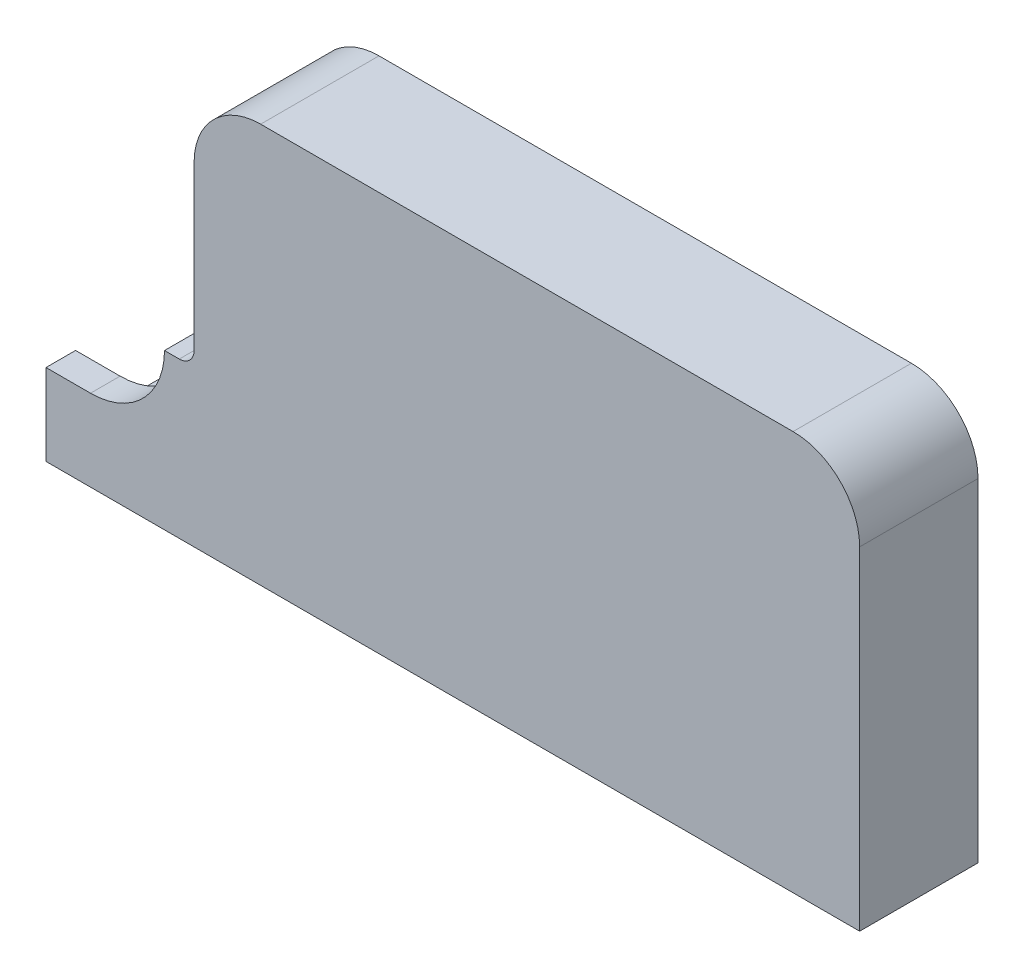
SolidWorks part; units mm, degrees
ref_plane "Front Plane" through (0, 0, 0) normal (0, 0, 1) x (1, 0, 0)
ref_plane "Top Plane" through (0, 0, 0) normal (0, 1, 0) x (1, 0, 0)
ref_plane "Right Plane" through (0, 0, 0) normal (1, 0, 0) x (0, 0, -1)
sketch "Sketch1" plane through (0, 0, 0) normal (0, 0, 1) x (1, 0, 0)
  line L30 (11.5095, 13.5276) -> (11.5095, 22.5276)
  line L31 (15.0095, 26.0276) -> (51, 26.0276)
  line L32 (54.5, 22.5276) -> (54.5, 1.0276)
  line L33 (54.5, 1.0276) -> (1.5, 1.0276)
  line L35 (0.5, 0.0276) -> (0.5, 5.5276)
  line L36 (55.5, 0.0276) -> (0.5, 0.0276)
  line L37 (55.5, 22.5276) -> (55.5, 0.0276)
  line L38 (15.0095, 27.0276) -> (51, 27.0276)
  line L39 (10.5095, 11.5276) -> (10.5095, 22.5276)
  line L40 (0.5, 0.0276) -> (0.5, 1.0276)
  line L41 (55.5, 0.0276) -> (0.5, 0.0276)
  line L42 (55.5, 22.5276) -> (55.5, 0.0276)
  line L43 (15.0095, 27.0276) -> (51, 27.0276)
  line L44 (10.5095, 13.5276) -> (10.5095, 22.5276)
  line L46 (10.5095, 13.5276) -> (11.5095, 13.5276)
  line L47 (8.5095, 11.5276) -> (10.0095, 11.5276) construction
  line L48 (10.5095, 11.5276) -> (10.5095, 22.5276) construction
  line L49 (11.5095, 11.5276) -> (11.5095, 22.5276) construction
  line L50 (1.5, 1.0276) -> (0.5, 1.0276)
  line L52 (0.5, 0.0276) -> (0.5, 5.5276) construction
  line L55 (1.5, 1.0276) -> (1.5, 5.5276) construction
  arc A13 (15.0095, 26.0276) -> (11.5095, 22.5276) centre (15.0095, 22.5276) ccw
  arc A14 (54.5, 22.5276) -> (51, 26.0276) centre (51, 22.5276) ccw
  arc A15 (55.5, 22.5276) -> (51, 27.0276) centre (51, 22.5276) ccw
  arc A16 (15.0095, 27.0276) -> (10.5095, 22.5276) centre (15.0095, 22.5276) ccw
  arc A17 (55.5, 22.5276) -> (51, 27.0276) centre (51, 22.5276) ccw
  arc A18 (15.0095, 27.0276) -> (10.5095, 22.5276) centre (15.0095, 22.5276) ccw
  dimension "D3" = 2
  dimension "D1" = 0.5
  dimension "D2" = 1
extrude "Boss-Extrude1" add sketch "Sketch1" along normal up to surface (8 mm away) from offset 5
sketch "Sketch2" plane through (0, 0, 13) normal (0, 0, 1) x (1, 0, 0)
  line L0 (0.5, 5.5276) -> (8.5095, 5.5276)
  line L1 (8.5095, 5.5276) -> (8.5095, 10.5276)
  line L2 (8.5095, 5.5276) -> (8.5095, 11.5276) construction
  line L3 (8.5095, 10.5276) -> (10.5095, 10.5276)
  line L4 (10.5095, 10.5276) -> (10.5095, 13.5276)
  line L5 (8.5095, 11.5276) -> (10.0095, 11.5276) construction
  line L6 (10.5095, 22.5276) -> (10.5095, 13.5276) construction
  line L7 (0.5, 1.0276) -> (0.5, 5.5276)
  line L8 (0, 5.5276) -> (3.5095, 5.5276) construction
  line L19 (11.5095, 13.5276) -> (11.5095, 22.5276)
  line L20 (15.0095, 26.0276) -> (51, 26.0276)
  line L21 (54.5, 22.5276) -> (54.5, 1.0276)
  line L22 (54.5, 1.0276) -> (0.5, 1.0276)
  line L25 (0.5, 1.0276) -> (0.5, 0.0276)
  line L26 (0.5, 0.0276) -> (55.5, 0.0276)
  line L27 (55.5, 0.0276) -> (55.5, 22.5276)
  line L28 (51, 27.0276) -> (15.0095, 27.0276)
  line L29 (10.5095, 22.5276) -> (10.5095, 13.5276)
  line L30 (10.5095, 13.5276) -> (11.5095, 13.5276)
  line L37 (0.5, 1.0276) -> (0.5, 0.0276)
  line L38 (0.5, 0.0276) -> (55.5, 0.0276)
  line L39 (55.5, 0.0276) -> (55.5, 22.5276)
  line L40 (51, 27.0276) -> (15.0095, 27.0276)
  line L41 (10.5095, 22.5276) -> (10.5095, 13.5276)
  arc A4 (15.0095, 26.0276) -> (11.5095, 22.5276) centre (15.0095, 22.5276) ccw
  arc A5 (54.5, 22.5276) -> (51, 26.0276) centre (51, 22.5276) ccw
  arc A6 (55.5, 22.5276) -> (51, 27.0276) centre (51, 22.5276) ccw
  arc A7 (15.0095, 27.0276) -> (10.5095, 22.5276) centre (15.0095, 22.5276) ccw
  arc A10 (55.5, 22.5276) -> (51, 27.0276) centre (51, 22.5276) ccw
  arc A11 (15.0095, 27.0276) -> (10.5095, 22.5276) centre (15.0095, 22.5276) ccw
  dimension "D1" = 1
  dimension "D2" = 0
extrude "Boss-Extrude2" add sketch "Sketch2" against normal blind 2
sketch "Sketch3" plane through (0, 0, 13) normal (0, 0, 1) x (1, 0, 0)
  circle A0 centre (29.6764, 8.283) radius 2 construction
  circle A1 centre (29.6764, 8.283) radius 2
extrude "Cut-Extrude1" [suppressed] cut sketch "Sketch3" against normal up to next
fillet "Fillet1" radius 5 1 edges at (8.5095, 5.5276, 12)
fillet "Fillet2" radius 1 1 edges at (10.5095, 10.5276, 12)
fillet "Fillet3" radius 1 6 edges at (11.5095, 18.0276, 11) (12.5346, 25.0024, 11) (54.5, 11.7776, 11) (53.4749, 25.0024, 11) (27.5, 1.0276, 11) (33.0047, 26.0276, 11)
sketch "Sketch4" plane through (0, 0, 13) normal (0, 0, 1) x (1, 0, 0)
  line L7 (10.5095, 22.5276) -> (10.5095, 11.5276)
  line L8 (9.5095, 10.5276) -> (8.5095, 10.5276)
  line L9 (3.5095, 5.5276) -> (0.5, 5.5276)
  line L10 (0.5, 5.5276) -> (0.5, 0.0276)
  line L11 (0.5, 0.0276) -> (55.5, 0.0276)
  line L12 (55.5, 0.0276) -> (55.5, 22.5276)
  line L13 (51, 27.0276) -> (15.0095, 27.0276)
  line L14 (10.5095, 22.5276) -> (10.5095, 11.5276)
  line L15 (9.5095, 10.5276) -> (8.5095, 10.5276)
  line L16 (3.5095, 5.5276) -> (0.5, 5.5276)
  line L17 (0.5, 5.5276) -> (0.5, 0.0276)
  line L18 (0.5, 0.0276) -> (55.5, 0.0276)
  line L19 (55.5, 0.0276) -> (55.5, 22.5276)
  line L20 (51, 27.0276) -> (15.0095, 27.0276)
  arc A4 (9.5095, 10.5276) -> (10.5095, 11.5276) centre (9.5095, 11.5276) ccw
  arc A5 (3.5095, 5.5276) -> (8.5095, 10.5276) centre (3.5095, 10.5276) ccw
  arc A6 (55.5, 22.5276) -> (51, 27.0276) centre (51, 22.5276) ccw
  arc A7 (15.0095, 27.0276) -> (10.5095, 22.5276) centre (15.0095, 22.5276) ccw
  arc A8 (9.5095, 10.5276) -> (10.5095, 11.5276) centre (9.5095, 11.5276) ccw
  arc A9 (3.5095, 5.5276) -> (8.5095, 10.5276) centre (3.5095, 10.5276) ccw
  arc A10 (55.5, 22.5276) -> (51, 27.0276) centre (51, 22.5276) ccw
  arc A11 (15.0095, 27.0276) -> (10.5095, 22.5276) centre (15.0095, 22.5276) ccw
  dimension "D1" = 0
sketch "Sketch6" plane through (0, 0, 13) normal (0, 0, 1) x (1, 0, 0)
  line L0 (30.8689, 19.9892) -> (35.2853, 19.9892) construction
  line L1 (30.8689, 21.681) -> (35.2853, 21.681) construction
  line L2 (30.8689, 18.2974) -> (35.2853, 18.2974) construction
  line L3 (30.8689, 22.681) -> (35.2853, 22.681)
  line L4 (30.8689, 17.2974) -> (35.2853, 17.2974)
  line L7 (10.5095, 22.5276) -> (10.5095, 11.5276)
  line L8 (9.5095, 10.5276) -> (8.5095, 10.5276)
  line L9 (3.5095, 5.5276) -> (0.5, 5.5276)
  line L10 (0.5, 5.5276) -> (0.5, 0.0276)
  line L11 (0.5, 0.0276) -> (55.5, 0.0276)
  line L12 (55.5, 0.0276) -> (55.5, 22.5276)
  line L13 (51, 27.0276) -> (15.0095, 27.0276)
  line L14 (10.5095, 22.5276) -> (10.5095, 11.5276)
  line L15 (9.5095, 10.5276) -> (8.5095, 10.5276)
  line L16 (3.5095, 5.5276) -> (0.5, 5.5276)
  line L17 (0.5, 5.5276) -> (0.5, 0.0276)
  line L18 (0.5, 0.0276) -> (55.5, 0.0276)
  line L19 (55.5, 0.0276) -> (55.5, 22.5276)
  line L20 (51, 27.0276) -> (15.0095, 27.0276)
  arc A0 (30.8689, 21.681) -> (30.8689, 18.2974) centre (30.8689, 19.9892) ccw construction
  arc A1 (35.2853, 18.2974) -> (35.2853, 21.681) centre (35.2853, 19.9892) ccw construction
  arc A2 (35.2853, 17.2974) -> (35.2853, 22.681) centre (35.2853, 19.9892) ccw
  arc A3 (30.8689, 22.681) -> (30.8689, 17.2974) centre (30.8689, 19.9892) ccw
  arc A4 (9.5095, 10.5276) -> (10.5095, 11.5276) centre (9.5095, 11.5276) ccw
  arc A5 (3.5095, 5.5276) -> (8.5095, 10.5276) centre (3.5095, 10.5276) ccw
  arc A6 (55.5, 22.5276) -> (51, 27.0276) centre (51, 22.5276) ccw
  arc A7 (15.0095, 27.0276) -> (10.5095, 22.5276) centre (15.0095, 22.5276) ccw
  arc A8 (9.5095, 10.5276) -> (10.5095, 11.5276) centre (9.5095, 11.5276) ccw
  arc A9 (3.5095, 5.5276) -> (8.5095, 10.5276) centre (3.5095, 10.5276) ccw
  arc A10 (55.5, 22.5276) -> (51, 27.0276) centre (51, 22.5276) ccw
  arc A11 (15.0095, 27.0276) -> (10.5095, 22.5276) centre (15.0095, 22.5276) ccw
  point P12 (33.0771, 19.9892)
  dimension "D1" = 0
  dimension "D2" = 1
extrude "Cut-Extrude2" [suppressed] cut sketch "Sketch6" against normal up to next contours L4 A2 L3 A3
chamfer "Chamfer1" [suppressed] distance 2 angle 45
